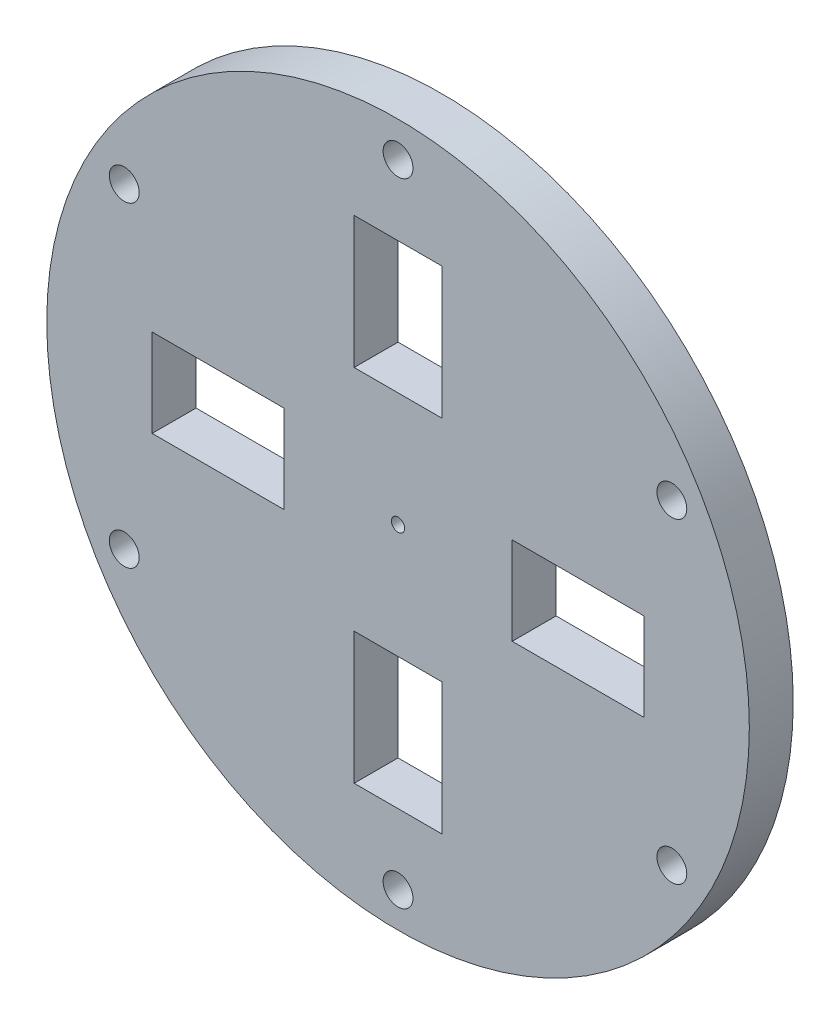
SolidWorks part; units mm, degrees
ref_plane "Front Plane" through (0, 0, 0) normal (0, 0, 1) x (1, 0, 0)
ref_plane "Top Plane" through (0, 0, 0) normal (0, 1, 0) x (1, 0, 0)
ref_plane "Right Plane" through (0, 0, 0) normal (1, 0, 0) x (0, 0, -1)
sketch "Sketch1" plane through (0, 0, 0) normal (0, 0, 1) x (1, 0, 0)
  circle A0 centre (0, 0) radius 40
  circle A1 centre (0, 0) radius 0.75
  dimension "D1" = 80
  dimension "D2" = 1.5
extrude "Boss-Extrude1" add sketch "Sketch1" along normal blind 5
sketch "Sketch4" plane through (0, 0, 5) normal (0, 0, 1) x (1, 0, 0)
  line L0 (0, 1040) -> (0, 28) construction
  line L1 (0, 0) -> (40, 0) construction
  line L2 (-5, 28) -> (-5, 13)
  line L3 (-5, 28) -> (5, 28)
  line L4 (13, 5) -> (13, -5)
  line L5 (-5, 13) -> (5, 13)
  line L6 (5, 28) -> (5, 13)
  line L7 (0, 13) -> (0, -40) construction
  line L8 (28, 5) -> (13, 5)
  line L9 (28, -5) -> (13, -5)
  line L10 (28, 5) -> (28, -5)
  line L11 (5, -13) -> (-5, -13)
  line L12 (5, -28) -> (5, -13)
  line L13 (-5, -28) -> (-5, -13)
  line L14 (5, -28) -> (-5, -28)
  line L15 (-13, -5) -> (-13, 5)
  line L16 (-28, -5) -> (-13, -5)
  line L17 (-28, 5) -> (-13, 5)
  line L18 (-28, -5) -> (-28, 5)
  point P12 (0, 0)
  dimension "D1" = 15
  dimension "D2" = 10
  dimension "D3" = 4
  dimension "D4" = 13
extrude "Cut-Extrude3" cut sketch "Sketch4" against normal through all
sketch "Sketch5" plane through (0, 0, 5) normal (0, 0, 1) x (1, 0, 0)
  line L0 (0, 0) -> (0, 40) construction
  circle A2 centre (0, 0) radius 40 construction
  circle A3 centre (0, 36) radius 1.7
  circle A4 centre (31.1769, 18) radius 1.7
  circle A5 centre (31.1769, -18) radius 1.7
  circle A6 centre (0, -36) radius 1.7
  circle A7 centre (-31.1769, -18) radius 1.7
  circle A8 centre (-31.1769, 18) radius 1.7
  dimension "D1" = 3.4
  dimension "D2" = 4
  dimension "D3" = 6
extrude "Cut-Extrude4" cut sketch "Sketch5" against normal through all
